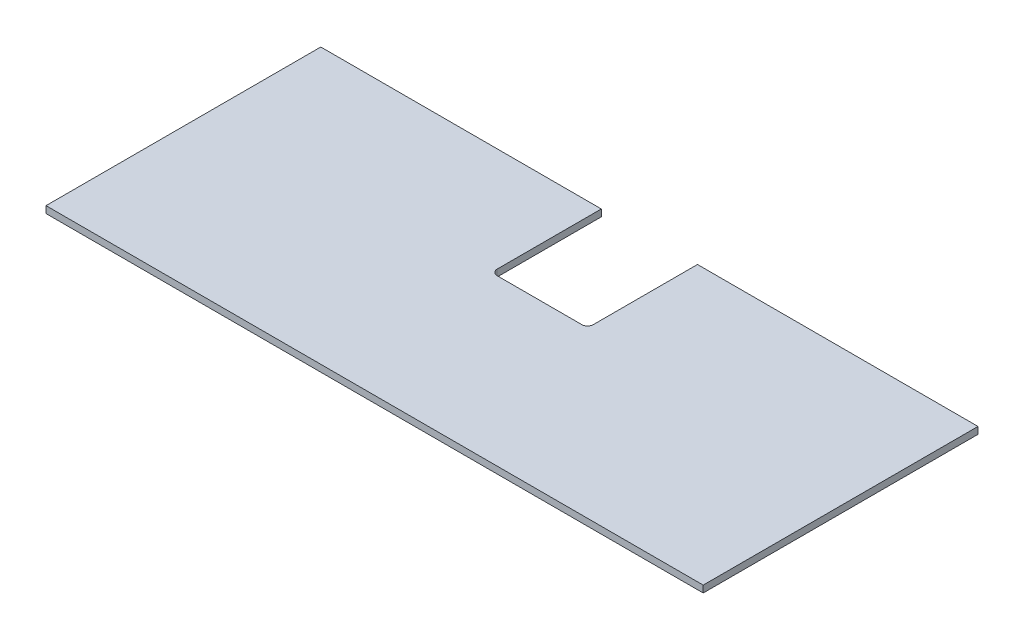
SolidWorks part; units mm, degrees
material "Acrílico (Impacto medio-alto)"
ref_plane "Alzado" through (0, 0, 0) normal (0, 0, 1) x (1, 0, 0)
ref_plane "Planta" through (0, 0, 0) normal (0, 1, 0) x (1, 0, 0)
ref_plane "Vista lateral" through (0, 0, 0) normal (1, 0, 0) x (0, 0, -1)
sketch "Sketch1" plane through (0, 0, 0) normal (0, 1, 0) x (1, 0, 0)
  line L1 (-143.5, -60) -> (143.5, -60)
  line L2 (-143.5, -60) -> (-143.5, 60)
  line L3 (-143.5, 60) -> (143.5, 60)
  line L4 (143.5, -60) -> (143.5, 60)
  line L5 (-143.5, -60) -> (143.5, 60) construction
  line L6 (-143.5, 60) -> (143.5, -60) construction
  point P0 (0, 0)
  dimension "D1" = 120
  dimension "D2" = 287
extrude "Boss-Extrude1" add sketch "Sketch1" along normal blind 3
sketch "Sketch2" plane through (0, 3, 0) normal (0, 1, 0) x (1, 0, 0)
  line L0 (0, 0) -> (0, 33) construction
  line L1 (-21, 12) -> (21, 12)
  line L2 (-21, 12) -> (-21, 54)
  line L3 (-21, 54) -> (21, 54) construction
  line L4 (21, 12) -> (21, 54)
  line L5 (-21, 12) -> (21, 54) construction
  line L6 (-21, 54) -> (21, 12) construction
  line L7 (143.5, 60) -> (-143.5, 60) construction
  line L8 (-21, 54) -> (-21, 60)
  line L9 (-21, 60) -> (21, 60)
  line L10 (21, 60) -> (21, 54)
  point P0 (0, 33)
  dimension "D1" = 42
  dimension "D2" = 42
  dimension "D3" = 6
extrude "Cut-Extrude1" cut sketch "Sketch2" against normal through all
fillet "Fillet1" radius 2.5 2 edges at (-21, 1.5, -12) (21, 1.5, -12)
